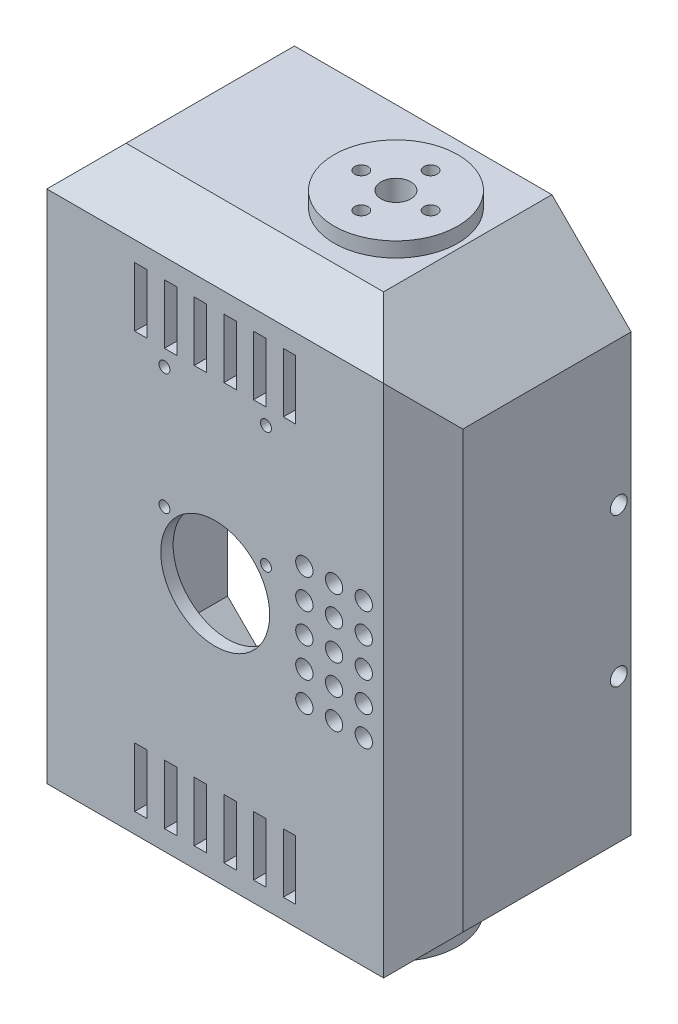
SolidWorks part; units mm, degrees
ref_plane "Front Plane" through (0, 0, 0) normal (0, 0, 1) x (1, 0, 0)
ref_plane "Top Plane" through (0, 0, 0) normal (0, 1, 0) x (1, 0, 0)
ref_plane "Right Plane" through (0, 0, 0) normal (1, 0, 0) x (0, 0, -1)
ref_plane "PZ_p168_000" through (0, 0, 168) normal (0, 0, 1) x (1, 0, 0)
sketch "S_prism1" plane through (0, 0, 168) normal (0, 0, 1) x (1, 0, 0)
  line L0 (42, -44) -> (42, 44)
  line L1 (42, 44) -> (26, 60)
  line L2 (26, 60) -> (-26, 60)
  line L3 (-26, 60) -> (-42, 44)
  line L4 (-42, 44) -> (-42, -44)
  line L5 (-42, -44) -> (-26, -60)
  line L6 (-26, -60) -> (26, -60)
  line L7 (26, -60) -> (42, -44)
extrude "Boss_1" add sketch "S_prism1" along normal blind 42
ref_plane "PX_m43_000" through (-43, 0, 0) normal (1, 0, 0) x (0, 0, -1)
sketch "S_pcut2" plane through (-43, 0, 0) normal (1, 0, 0) x (0, 0, -1)
  line L0 (-210.6, 60.6) -> (-210.6, 51.4)
  line L1 (-210.6, 51.4) -> (-201.4, 60.6)
  line L2 (-201.4, 60.6) -> (-210.6, 60.6)
extrude "Cut_2" cut sketch "S_pcut2" along normal blind 86
sketch "S_pcut3" plane through (-43, 0, 0) normal (1, 0, 0) x (0, 0, -1)
  line L0 (-210.6, -60.6) -> (-210.6, -51.4)
  line L1 (-210.6, -51.4) -> (-201.4, -60.6)
  line L2 (-201.4, -60.6) -> (-210.6, -60.6)
extrude "Cut_3" cut sketch "S_pcut3" along normal blind 86
ref_plane "PY_m61_000" through (0, -61, 0) normal (0, 1, 0) x (1, 0, 0)
sketch "S_pcut4" plane through (0, -61, 0) normal (0, 1, 0) x (1, 0, 0)
  line L0 (42.6, -210.6) -> (33.4, -210.6)
  line L1 (33.4, -210.6) -> (42.6, -201.4)
  line L2 (42.6, -201.4) -> (42.6, -210.6)
extrude "Cut_4" cut sketch "S_pcut4" along normal blind 122
sketch "S_pcut5" plane through (0, -61, 0) normal (0, 1, 0) x (1, 0, 0)
  line L0 (-42.6, -210.6) -> (-33.4, -210.6)
  line L1 (-33.4, -210.6) -> (-42.6, -201.4)
  line L2 (-42.6, -201.4) -> (-42.6, -210.6)
extrude "Cut_5" cut sketch "S_pcut5" along normal blind 122
ref_plane "PZ_p167_900" through (0, 0, 167.9) normal (0, 0, 1) x (1, 0, 0)
sketch "S_pcut6" plane through (0, 0, 167.9) normal (0, 0, 1) x (1, 0, 0)
  line L0 (39.5, -42.9645) -> (39.5, 42.9645)
  line L1 (39.5, 42.9645) -> (24.9645, 57.5)
  line L2 (24.9645, 57.5) -> (-24.9645, 57.5)
  line L3 (-24.9645, 57.5) -> (-39.5, 42.9645)
  line L4 (-39.5, 42.9645) -> (-39.5, -42.9645)
  line L5 (-39.5, -42.9645) -> (-24.9645, -57.5)
  line L6 (-24.9645, -57.5) -> (24.9645, -57.5)
  line L7 (24.9645, -57.5) -> (39.5, -42.9645)
extrude "Cut_6" cut sketch "S_pcut6" along normal blind 31.6
ref_plane "PZ_p199_400" through (0, 0, 199.4) normal (0, 0, 1) x (1, 0, 0)
sketch "S_pcut7" plane through (0, 0, 199.4) normal (0, 0, 1) x (1, 0, 0)
  line L0 (35.5, -41.3076) -> (35.5, 41.3076)
  line L1 (35.5, 41.3076) -> (23.3076, 53.5)
  line L2 (23.3076, 53.5) -> (-23.3076, 53.5)
  line L3 (-23.3076, 53.5) -> (-35.5, 41.3076)
  line L4 (-35.5, 41.3076) -> (-35.5, -41.3076)
  line L5 (-35.5, -41.3076) -> (-23.3076, -53.5)
  line L6 (-23.3076, -53.5) -> (23.3076, -53.5)
  line L7 (23.3076, -53.5) -> (35.5, -41.3076)
extrude "Cut_7" cut sketch "S_pcut7" along normal blind 4.1
ref_plane "PZ_p203_400" through (0, 0, 203.4) normal (0, 0, 1) x (1, 0, 0)
sketch "S_pcut8" plane through (0, 0, 203.4) normal (0, 0, 1) x (1, 0, 0)
  line L0 (31.5, -39.6508) -> (31.5, 39.6508)
  line L1 (31.5, 39.6508) -> (21.6508, 49.5)
  line L2 (21.6508, 49.5) -> (-21.6508, 49.5)
  line L3 (-21.6508, 49.5) -> (-31.5, 39.6508)
  line L4 (-31.5, 39.6508) -> (-31.5, -39.6508)
  line L5 (-31.5, -39.6508) -> (-21.6508, -49.5)
  line L6 (-21.6508, -49.5) -> (21.6508, -49.5)
  line L7 (21.6508, -49.5) -> (31.5, -39.6508)
extrude "Cut_8" cut sketch "S_pcut8" along normal blind 4.1
ref_plane "PZ_p207_400" through (0, 0, 207.4) normal (0, 0, 1) x (1, 0, 0)
sketch "S_cut9" plane through (0, 0, 207.4) normal (0, 0, 1) x (1, 0, 0)
  line L0 (-16.25, 36) -> (-13.75, 36)
  line L1 (-13.75, 36) -> (-13.75, 48)
  line L2 (-13.75, 48) -> (-16.25, 48)
  line L3 (-16.25, 48) -> (-16.25, 36)
  dimension "P1" = 16.25
  dimension "P2" = 36
  dimension "P3" = 13.75
  dimension "P4" = 36
  dimension "P5" = 13.75
  dimension "P6" = 48
  dimension "P7" = 16.25
  dimension "P8" = 48
extrude "Pocket_9" cut sketch "S_cut9" along normal blind 2.7
sketch "S_cut10" plane through (0, 0, 207.4) normal (0, 0, 1) x (1, 0, 0)
  line L0 (-10.25, 36) -> (-7.75, 36)
  line L1 (-7.75, 36) -> (-7.75, 48)
  line L2 (-7.75, 48) -> (-10.25, 48)
  line L3 (-10.25, 48) -> (-10.25, 36)
  dimension "P1" = 10.25
  dimension "P2" = 36
  dimension "P3" = 7.75
  dimension "P4" = 36
  dimension "P5" = 7.75
  dimension "P6" = 48
  dimension "P7" = 10.25
  dimension "P8" = 48
extrude "Pocket_10" cut sketch "S_cut10" along normal blind 2.7
sketch "S_cut11" plane through (0, 0, 207.4) normal (0, 0, 1) x (1, 0, 0)
  line L0 (-4.25, 36) -> (-1.75, 36)
  line L1 (-1.75, 36) -> (-1.75, 48)
  line L2 (-1.75, 48) -> (-4.25, 48)
  line L3 (-4.25, 48) -> (-4.25, 36)
  dimension "P1" = 4.25
  dimension "P2" = 36
  dimension "P3" = 1.75
  dimension "P4" = 36
  dimension "P5" = 1.75
  dimension "P6" = 48
  dimension "P7" = 4.25
  dimension "P8" = 48
extrude "Pocket_11" cut sketch "S_cut11" along normal blind 2.7
sketch "S_cut12" plane through (0, 0, 207.4) normal (0, 0, 1) x (1, 0, 0)
  line L0 (1.75, 36) -> (4.25, 36)
  line L1 (4.25, 36) -> (4.25, 48)
  line L2 (4.25, 48) -> (1.75, 48)
  line L3 (1.75, 48) -> (1.75, 36)
  dimension "P1" = 1.75
  dimension "P2" = 36
  dimension "P3" = 4.25
  dimension "P4" = 36
  dimension "P5" = 4.25
  dimension "P6" = 48
  dimension "P7" = 1.75
  dimension "P8" = 48
extrude "Pocket_12" cut sketch "S_cut12" along normal blind 2.7
sketch "S_cut13" plane through (0, 0, 207.4) normal (0, 0, 1) x (1, 0, 0)
  line L0 (7.75, 36) -> (10.25, 36)
  line L1 (10.25, 36) -> (10.25, 48)
  line L2 (10.25, 48) -> (7.75, 48)
  line L3 (7.75, 48) -> (7.75, 36)
  dimension "P1" = 7.75
  dimension "P2" = 36
  dimension "P3" = 10.25
  dimension "P4" = 36
  dimension "P5" = 10.25
  dimension "P6" = 48
  dimension "P7" = 7.75
  dimension "P8" = 48
extrude "Pocket_13" cut sketch "S_cut13" along normal blind 2.7
sketch "S_cut14" plane through (0, 0, 207.4) normal (0, 0, 1) x (1, 0, 0)
  line L0 (13.75, 36) -> (16.25, 36)
  line L1 (16.25, 36) -> (16.25, 48)
  line L2 (16.25, 48) -> (13.75, 48)
  line L3 (13.75, 48) -> (13.75, 36)
  dimension "P1" = 13.75
  dimension "P2" = 36
  dimension "P3" = 16.25
  dimension "P4" = 36
  dimension "P5" = 16.25
  dimension "P6" = 48
  dimension "P7" = 13.75
  dimension "P8" = 48
extrude "Pocket_14" cut sketch "S_cut14" along normal blind 2.7
ref_plane "PX_p39_400" through (39.4, 0, 0) normal (1, 0, 0) x (0, 0, -1)
sketch "S_hole15" plane through (39.4, 0, 0) normal (1, 0, 0) x (0, 0, -1)
  circle A0 centre (-170.5, -15) radius 1.7
  dimension "D1_S_hole15" = 3.4
  dimension "P2" = 170.5
  dimension "P3" = 15
extrude "Hole_15" cut sketch "S_hole15" along normal blind 2.7
sketch "S_hole16" plane through (39.4, 0, 0) normal (1, 0, 0) x (0, 0, -1)
  circle A0 centre (-170.5, 15) radius 1.7
  dimension "D1_S_hole16" = 3.4
  dimension "P2" = 170.5
  dimension "P3" = 15
extrude "Hole_16" cut sketch "S_hole16" along normal blind 2.7
sketch "S_cut17" plane through (0, 0, 207.4) normal (0, 0, 1) x (1, 0, 0)
  line L0 (-16.25, -48) -> (-13.75, -48)
  line L1 (-13.75, -48) -> (-13.75, -36)
  line L2 (-13.75, -36) -> (-16.25, -36)
  line L3 (-16.25, -36) -> (-16.25, -48)
  dimension "P1" = 16.25
  dimension "P2" = 48
  dimension "P3" = 13.75
  dimension "P4" = 48
  dimension "P5" = 13.75
  dimension "P6" = 36
  dimension "P7" = 16.25
  dimension "P8" = 36
extrude "Pocket_17" cut sketch "S_cut17" along normal blind 2.7
sketch "S_cut18" plane through (0, 0, 207.4) normal (0, 0, 1) x (1, 0, 0)
  line L0 (-10.25, -48) -> (-7.75, -48)
  line L1 (-7.75, -48) -> (-7.75, -36)
  line L2 (-7.75, -36) -> (-10.25, -36)
  line L3 (-10.25, -36) -> (-10.25, -48)
  dimension "P1" = 10.25
  dimension "P2" = 48
  dimension "P3" = 7.75
  dimension "P4" = 48
  dimension "P5" = 7.75
  dimension "P6" = 36
  dimension "P7" = 10.25
  dimension "P8" = 36
extrude "Pocket_18" cut sketch "S_cut18" along normal blind 2.7
sketch "S_cut19" plane through (0, 0, 207.4) normal (0, 0, 1) x (1, 0, 0)
  line L0 (-4.25, -48) -> (-1.75, -48)
  line L1 (-1.75, -48) -> (-1.75, -36)
  line L2 (-1.75, -36) -> (-4.25, -36)
  line L3 (-4.25, -36) -> (-4.25, -48)
  dimension "P1" = 4.25
  dimension "P2" = 48
  dimension "P3" = 1.75
  dimension "P4" = 48
  dimension "P5" = 1.75
  dimension "P6" = 36
  dimension "P7" = 4.25
  dimension "P8" = 36
extrude "Pocket_19" cut sketch "S_cut19" along normal blind 2.7
sketch "S_cut20" plane through (0, 0, 207.4) normal (0, 0, 1) x (1, 0, 0)
  line L0 (1.75, -48) -> (4.25, -48)
  line L1 (4.25, -48) -> (4.25, -36)
  line L2 (4.25, -36) -> (1.75, -36)
  line L3 (1.75, -36) -> (1.75, -48)
  dimension "P1" = 1.75
  dimension "P2" = 48
  dimension "P3" = 4.25
  dimension "P4" = 48
  dimension "P5" = 4.25
  dimension "P6" = 36
  dimension "P7" = 1.75
  dimension "P8" = 36
extrude "Pocket_20" cut sketch "S_cut20" along normal blind 2.7
sketch "S_cut21" plane through (0, 0, 207.4) normal (0, 0, 1) x (1, 0, 0)
  line L0 (7.75, -48) -> (10.25, -48)
  line L1 (10.25, -48) -> (10.25, -36)
  line L2 (10.25, -36) -> (7.75, -36)
  line L3 (7.75, -36) -> (7.75, -48)
  dimension "P1" = 7.75
  dimension "P2" = 48
  dimension "P3" = 10.25
  dimension "P4" = 48
  dimension "P5" = 10.25
  dimension "P6" = 36
  dimension "P7" = 7.75
  dimension "P8" = 36
extrude "Pocket_21" cut sketch "S_cut21" along normal blind 2.7
sketch "S_cut22" plane through (0, 0, 207.4) normal (0, 0, 1) x (1, 0, 0)
  line L0 (13.75, -48) -> (16.25, -48)
  line L1 (16.25, -48) -> (16.25, -36)
  line L2 (16.25, -36) -> (13.75, -36)
  line L3 (13.75, -36) -> (13.75, -48)
  dimension "P1" = 13.75
  dimension "P2" = 48
  dimension "P3" = 16.25
  dimension "P4" = 48
  dimension "P5" = 16.25
  dimension "P6" = 36
  dimension "P7" = 13.75
  dimension "P8" = 36
extrude "Pocket_22" cut sketch "S_cut22" along normal blind 2.7
ref_plane "PX_m42_100" through (-42.1, 0, 0) normal (1, 0, 0) x (0, 0, -1)
sketch "S_hole23" plane through (-42.1, 0, 0) normal (1, 0, 0) x (0, 0, -1)
  circle A0 centre (-170.5, -15) radius 1.7
  dimension "D1_S_hole23" = 3.4
  dimension "P2" = 170.5
  dimension "P3" = 15
extrude "Hole_23" cut sketch "S_hole23" along normal blind 2.7
sketch "S_hole24" plane through (-42.1, 0, 0) normal (1, 0, 0) x (0, 0, -1)
  circle A0 centre (-170.5, 15) radius 1.7
  dimension "D1_S_hole24" = 3.4
  dimension "P2" = 170.5
  dimension "P3" = 15
extrude "Hole_24" cut sketch "S_hole24" along normal blind 2.7
sketch "S_hole25" plane through (0, 0, 207.4) normal (0, 0, 1) x (1, 0, 0)
  circle A0 centre (18, -12) radius 1.75
  dimension "D1_S_hole25" = 3.5
  dimension "P2" = 18
  dimension "P3" = 12
extrude "Hole_25" cut sketch "S_hole25" along normal blind 2.7
sketch "S_hole26" plane through (0, 0, 207.4) normal (0, 0, 1) x (1, 0, 0)
  circle A0 centre (18, -6) radius 1.75
  dimension "D1_S_hole26" = 3.5
  dimension "P2" = 18
  dimension "P3" = 6
extrude "Hole_26" cut sketch "S_hole26" along normal blind 2.7
sketch "S_hole27" plane through (0, 0, 207.4) normal (0, 0, 1) x (1, 0, 0)
  circle A0 centre (18, 0) radius 1.75
  dimension "D1_S_hole27" = 3.5
  dimension "P2" = 18
extrude "Hole_27" cut sketch "S_hole27" along normal blind 2.7
sketch "S_hole28" plane through (0, 0, 207.4) normal (0, 0, 1) x (1, 0, 0)
  circle A0 centre (18, 6) radius 1.75
  dimension "D1_S_hole28" = 3.5
  dimension "P2" = 18
  dimension "P3" = 6
extrude "Hole_28" cut sketch "S_hole28" along normal blind 2.7
sketch "S_hole29" plane through (0, 0, 207.4) normal (0, 0, 1) x (1, 0, 0)
  circle A0 centre (18, 12) radius 1.75
  dimension "D1_S_hole29" = 3.5
  dimension "P2" = 18
  dimension "P3" = 12
extrude "Hole_29" cut sketch "S_hole29" along normal blind 2.7
sketch "S_hole30" plane through (0, 0, 207.4) normal (0, 0, 1) x (1, 0, 0)
  circle A0 centre (24, -12) radius 1.75
  dimension "D1_S_hole30" = 3.5
  dimension "P2" = 24
  dimension "P3" = 12
extrude "Hole_30" cut sketch "S_hole30" along normal blind 2.7
sketch "S_hole31" plane through (0, 0, 207.4) normal (0, 0, 1) x (1, 0, 0)
  circle A0 centre (24, -6) radius 1.75
  dimension "D1_S_hole31" = 3.5
  dimension "P2" = 24
  dimension "P3" = 6
extrude "Hole_31" cut sketch "S_hole31" along normal blind 2.7
sketch "S_hole32" plane through (0, 0, 207.4) normal (0, 0, 1) x (1, 0, 0)
  circle A0 centre (24, 0) radius 1.75
  dimension "D1_S_hole32" = 3.5
  dimension "P2" = 24
extrude "Hole_32" cut sketch "S_hole32" along normal blind 2.7
sketch "S_hole33" plane through (0, 0, 207.4) normal (0, 0, 1) x (1, 0, 0)
  circle A0 centre (24, 6) radius 1.75
  dimension "D1_S_hole33" = 3.5
  dimension "P2" = 24
  dimension "P3" = 6
extrude "Hole_33" cut sketch "S_hole33" along normal blind 2.7
sketch "S_hole34" plane through (0, 0, 207.4) normal (0, 0, 1) x (1, 0, 0)
  circle A0 centre (24, 12) radius 1.75
  dimension "D1_S_hole34" = 3.5
  dimension "P2" = 24
  dimension "P3" = 12
extrude "Hole_34" cut sketch "S_hole34" along normal blind 2.7
sketch "S_hole35" plane through (0, 0, 207.4) normal (0, 0, 1) x (1, 0, 0)
  circle A0 centre (30, -12) radius 1.75
  dimension "D1_S_hole35" = 3.5
  dimension "P2" = 30
  dimension "P3" = 12
extrude "Hole_35" cut sketch "S_hole35" along normal blind 2.7
sketch "S_hole36" plane through (0, 0, 207.4) normal (0, 0, 1) x (1, 0, 0)
  circle A0 centre (30, -6) radius 1.75
  dimension "D1_S_hole36" = 3.5
  dimension "P2" = 30
  dimension "P3" = 6
extrude "Hole_36" cut sketch "S_hole36" along normal blind 2.7
sketch "S_hole37" plane through (0, 0, 207.4) normal (0, 0, 1) x (1, 0, 0)
  circle A0 centre (30, 0) radius 1.75
  dimension "D1_S_hole37" = 3.5
  dimension "P2" = 30
extrude "Hole_37" cut sketch "S_hole37" along normal blind 2.7
sketch "S_hole38" plane through (0, 0, 207.4) normal (0, 0, 1) x (1, 0, 0)
  circle A0 centre (30, 6) radius 1.75
  dimension "D1_S_hole38" = 3.5
  dimension "P2" = 30
  dimension "P3" = 6
extrude "Hole_38" cut sketch "S_hole38" along normal blind 2.7
sketch "S_hole39" plane through (0, 0, 207.4) normal (0, 0, 1) x (1, 0, 0)
  circle A0 centre (30, 12) radius 1.75
  dimension "D1_S_hole39" = 3.5
  dimension "P2" = 30
  dimension "P3" = 12
extrude "Hole_39" cut sketch "S_hole39" along normal blind 2.7
sketch "S_hole40" plane through (0, 0, 207.4) normal (0, 0, 1) x (1, 0, 0)
  circle A0 centre (0, 0) radius 11
  dimension "D1_S_hole40" = 22
extrude "Hole_40" cut sketch "S_hole40" along normal blind 2.7
sketch "S_hole41" plane through (0, 0, 207.4) normal (0, 0, 1) x (1, 0, 0)
  circle A0 centre (-10.25, 8.3) radius 1.1
  dimension "D1_S_hole41" = 2.2
  dimension "P2" = 10.25
  dimension "P3" = 8.3
extrude "Hole_41" cut sketch "S_hole41" along normal blind 2.7
sketch "S_hole42" plane through (0, 0, 207.4) normal (0, 0, 1) x (1, 0, 0)
  circle A0 centre (10.25, 8.3) radius 1.1
  dimension "D1_S_hole42" = 2.2
  dimension "P2" = 10.25
  dimension "P3" = 8.3
extrude "Hole_42" cut sketch "S_hole42" along normal blind 2.7
sketch "S_hole43" plane through (0, 0, 207.4) normal (0, 0, 1) x (1, 0, 0)
  circle A0 centre (-10.25, 32.75) radius 1.1
  dimension "D1_S_hole43" = 2.2
  dimension "P2" = 10.25
  dimension "P3" = 32.75
extrude "Hole_43" cut sketch "S_hole43" along normal blind 2.7
sketch "S_hole44" plane through (0, 0, 207.4) normal (0, 0, 1) x (1, 0, 0)
  circle A0 centre (10.25, 32.75) radius 1.1
  dimension "D1_S_hole44" = 2.2
  dimension "P2" = 10.25
  dimension "P3" = 32.75
extrude "Hole_44" cut sketch "S_hole44" along normal blind 2.7
ref_plane "PY_p57_000" through (0, 57, 0) normal (0, 1, 0) x (1, 0, 0)
sketch "S_cyl45" plane through (0, 57, 0) normal (0, 1, 0) x (1, 0, 0)
  circle A0 centre (12.5, -186) radius 12.5
  dimension "D1_S_cyl45" = 25
  dimension "P2" = 12.5
  dimension "P3" = 186
extrude "Boss_45" add sketch "S_cyl45" along normal blind 6
ref_plane "PY_m63_000" through (0, -63, 0) normal (0, 1, 0) x (1, 0, 0)
sketch "S_cyl46" plane through (0, -63, 0) normal (0, 1, 0) x (1, 0, 0)
  circle A0 centre (12.5, -186) radius 12.5
  dimension "D1_S_cyl46" = 25
  dimension "P2" = 12.5
  dimension "P3" = 186
extrude "Boss_46" add sketch "S_cyl46" along normal blind 6
ref_plane "PY_p56_900" through (0, 56.9, 0) normal (0, 1, 0) x (1, 0, 0)
sketch "S_hole47" plane through (0, 56.9, 0) normal (0, 1, 0) x (1, 0, 0)
  circle A0 centre (12.5, -186) radius 3
  dimension "D1_S_hole47" = 6
  dimension "P2" = 12.5
  dimension "P3" = 186
extrude "Hole_47" cut sketch "S_hole47" along normal blind 6.2
sketch "S_hole48" plane through (0, 56.9, 0) normal (0, 1, 0) x (1, 0, 0)
  circle A0 centre (19.5, -186) radius 1.35
  dimension "D1_S_hole48" = 2.7
  dimension "P2" = 19.5
  dimension "P3" = 186
extrude "Hole_48" cut sketch "S_hole48" along normal blind 6.2
sketch "S_hole49" plane through (0, 56.9, 0) normal (0, 1, 0) x (1, 0, 0)
  circle A0 centre (12.5, -193) radius 1.35
  dimension "D1_S_hole49" = 2.7
  dimension "P2" = 12.5
  dimension "P3" = 193
extrude "Hole_49" cut sketch "S_hole49" along normal blind 6.2
sketch "S_hole50" plane through (0, 56.9, 0) normal (0, 1, 0) x (1, 0, 0)
  circle A0 centre (5.5, -186) radius 1.35
  dimension "D1_S_hole50" = 2.7
  dimension "P2" = 5.5
  dimension "P3" = 186
extrude "Hole_50" cut sketch "S_hole50" along normal blind 6.2
sketch "S_hole51" plane through (0, 56.9, 0) normal (0, 1, 0) x (1, 0, 0)
  circle A0 centre (12.5, -179) radius 1.35
  dimension "D1_S_hole51" = 2.7
  dimension "P2" = 12.5
  dimension "P3" = 179
extrude "Hole_51" cut sketch "S_hole51" along normal blind 6.2
ref_plane "PY_m63_100" through (0, -63.1, 0) normal (0, 1, 0) x (1, 0, 0)
sketch "S_hole52" plane through (0, -63.1, 0) normal (0, 1, 0) x (1, 0, 0)
  circle A0 centre (12.5, -186) radius 3
  dimension "D1_S_hole52" = 6
  dimension "P2" = 12.5
  dimension "P3" = 186
extrude "Hole_52" cut sketch "S_hole52" along normal blind 6.2
sketch "S_hole53" plane through (0, -63.1, 0) normal (0, 1, 0) x (1, 0, 0)
  circle A0 centre (19.5, -186) radius 1.35
  dimension "D1_S_hole53" = 2.7
  dimension "P2" = 19.5
  dimension "P3" = 186
extrude "Hole_53" cut sketch "S_hole53" along normal blind 6.2
sketch "S_hole54" plane through (0, -63.1, 0) normal (0, 1, 0) x (1, 0, 0)
  circle A0 centre (12.5, -193) radius 1.35
  dimension "D1_S_hole54" = 2.7
  dimension "P2" = 12.5
  dimension "P3" = 193
extrude "Hole_54" cut sketch "S_hole54" along normal blind 6.2
sketch "S_hole55" plane through (0, -63.1, 0) normal (0, 1, 0) x (1, 0, 0)
  circle A0 centre (5.5, -186) radius 1.35
  dimension "D1_S_hole55" = 2.7
  dimension "P2" = 5.5
  dimension "P3" = 186
extrude "Hole_55" cut sketch "S_hole55" along normal blind 6.2
sketch "S_hole56" plane through (0, -63.1, 0) normal (0, 1, 0) x (1, 0, 0)
  circle A0 centre (12.5, -179) radius 1.35
  dimension "D1_S_hole56" = 2.7
  dimension "P2" = 12.5
  dimension "P3" = 179
extrude "Hole_56" cut sketch "S_hole56" along normal blind 6.2
equation "\"plate_t\" = 3"
equation "\"clearance\" = 0.4"
